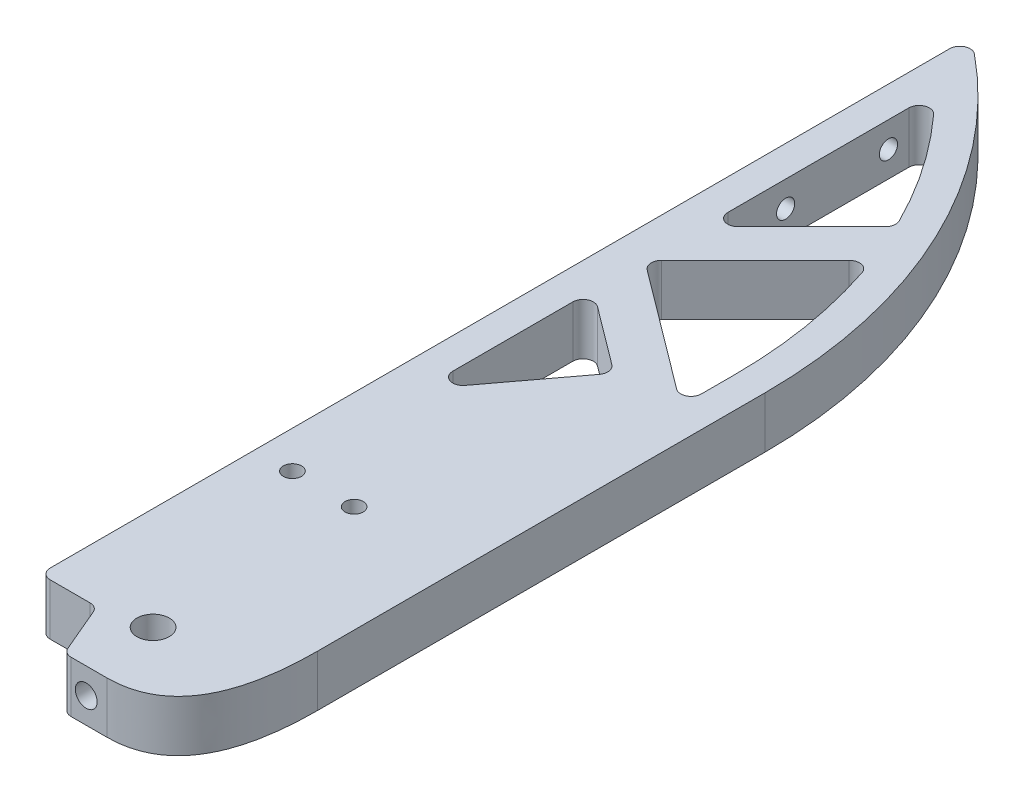
SolidWorks part; units mm, degrees
ref_plane "Front Plane" through (0, 0, 0) normal (0, 0, 1) x (1, 0, 0)
ref_plane "Top Plane" through (0, 0, 0) normal (0, 1, 0) x (1, 0, 0)
ref_plane "Right Plane" through (0, 0, 0) normal (1, 0, 0) x (0, 0, -1)
sketch "Sketch1" plane through (0, 0, 0) normal (0, 1, 0) x (1, 0, 0)
  line L1 (-25.4, -121.92) -> (25.4, -121.92)
  line L2 (-25.4, -121.92) -> (-25.4, 121.92)
  line L3 (-25.4, 121.92) -> (25.4, 121.92)
  line L4 (25.4, -121.92) -> (25.4, 121.92)
  line L5 (-25.4, -121.92) -> (25.4, 121.92) construction
  line L6 (-25.4, 121.92) -> (25.4, -121.92) construction
  point P0 (0, 0)
  dimension "D1" = 243.84
  dimension "D2" = 50.8
extrude "Boss-Extrude1" add sketch "Sketch1" along normal mid plane 12.7
sketch "Sketch2" plane through (0, 6.35, 0) normal (0, 1, 0) x (1, 0, 0)
  line L0 (0, 121.92) -> (0, -121.92) construction
  line L1 (25.4, 121.92) -> (-25.4, 121.92) construction
  line L2 (-25.4, -121.92) -> (25.4, -121.92) construction
  circle A0 centre (0, -105.41) radius 4
  dimension "D1" = 8
  dimension "D2" = 16.51
extrude "Pivot Point" cut sketch "Sketch2" against normal through all
sketch "Sketch3" plane through (0, 6.35, 0) normal (0, 1, 0) x (1, 0, 0)
  line L0 (0, -105.41) -> (0, -113.03) construction
  line L1 (0, -113.03) -> (-25.4, -113.03) construction
  line L2 (-25.4, 121.92) -> (-25.4, -121.92) construction
  line L3 (-25.4, -113.03) -> (-11.176, -113.03) construction
  line L4 (-11.176, -113.03) -> (-11.176, -121.92) construction
  line L5 (-25.4, -121.92) -> (25.4, -121.92) construction
  line L6 (-25.4, -107.95) -> (-9.8374, -107.95)
  line L7 (-9.8374, -107.95) -> (0, -105.41) construction
  line L8 (-6.7202, -113.03) -> (-2.9466, -121.92) construction
  line L10 (-25.4, -88.9) -> (-17.78, -88.9)
  line L11 (-17.78, -88.9) -> (-25.4, -25.4)
  line L12 (-25.4, -25.4) -> (-25.4, 121.92)
  line L13 (-25.4, 121.92) -> (25.4, 121.92)
  line L14 (25.4, 121.92) -> (25.4, 20.32)
  line L15 (25.4, -121.92) -> (25.4, 121.92) construction
  line L16 (25.4, -90.17) -> (25.4, -121.92)
  line L17 (25.4, -121.92) -> (5.08, -121.92)
  line L18 (-2.9466, -121.92) -> (-25.4, -121.92) construction
  line L19 (-25.4, -121.92) -> (-25.4, -25.4)
  line L21 (-11.3324, -107.95) -> (-5.4025, -121.92)
  line L22 (-5.4025, -121.92) -> (-25.4, -121.92)
  line L23 (-25.4, -25.4) -> (-25.4, -88.9)
  circle A0 centre (0, -105.41) radius 10.16 construction
  arc A1 (-9.8374, -107.95) -> (-6.7202, -113.03) centre (0, -105.41) ccw
  arc A2 (-25.4, 121.92) -> (25.4, 20.32) centre (-101.6, 20.32) cw
  spline S0 degree 2 poles (5.08, -121.92) (25.4, -121.92) (25.4, -90.17) knots 0 0 0 1 1 1
  line M22 (-25.4, 121.92) -> (-25.4, -121.92)
  line M23 (-25.4, -121.92) -> (25.4, -121.92)
  dimension "D1" = 7.62
  dimension "D4" = 20.32
  dimension "D6" = 7.62
  dimension "D7" = 63.5
  dimension "D9" = 31.75
  dimension "D10" = 20.32
  dimension "D11" = 101.6
  dimension "D12" = 2.2606
  dimension "D2" = 11.176
  dimension "D3" = 5.08
  dimension "D5" = 113
  dimension "D8" = 19.05
extrude "Main Shape" cut sketch "Sketch3" against normal through all contours A1 L6 L8 M22 M23 | S0 L16 L17 | A2 L14 L13 region at (-16.7977, 6.35, 115.3403)
sketch "Sketch12" plane through (-25.4, 0, 0) normal (-1, 0, 0) x (0, 0, 1)
  line L0 (-93.98, 0) -> (-68.58, 0)
  line L1 (-121.92, 6.35) -> (-121.92, -6.35) construction
  point P0 (-93.98, 0)
  point P2 (-68.58, 0)
  point P9 (-121.92, 0)
  dimension "D1" = 25.4
  dimension "D2" = 27.94
sketch "Sketch4" plane through (0, 6.35, 0) normal (0, 1, 0) x (1, 0, 0)
  line L0 (-17.78, 105.3247) -> (-17.78, 48.1747)
  line L1 (-17.78, 48.1747) -> (6.0241, 71.9788)
  line L2 (10.3072, 61.8935) -> (-17.78, 33.8062)
  line L3 (-17.78, 33.8062) -> (17.78, 7.1362)
  line L4 (17.78, 7.1362) -> (17.78, 20.32)
  line L5 (-17.78, 21.1062) -> (2.54, 5.8662)
  line L7 (-17.78, -21.2271) -> (-17.78, 21.1062)
  line L9 (2.54, 5.8662) -> (-17.78, -21.2271)
  line L32 (17.78, -90.17) -> (17.78, 20.32)
  line L33 (-17.78, 105.3247) -> (-17.78, -100.33)
  line L37 (-17.78, -100.33) -> (-6.2888, -100.33)
  line L38 (-6.2888, -100.33) -> (-0.3589, -114.3)
  line L39 (-0.3589, -114.3) -> (5.08, -114.3)
  line L40 (17.78, -90.17) -> (17.78, 20.32) construction
  line L41 (-17.78, 105.3247) -> (-17.78, -21.2271) construction
  line L45 (-17.78, -100.33) -> (-6.2888, -100.33) construction
  line L46 (-6.2888, -100.33) -> (-0.3589, -114.3) construction
  line L47 (-0.3589, -114.3) -> (5.08, -114.3) construction
  arc A0 (-17.78, 105.3247) -> (6.0241, 71.9788) centre (-101.6, 20.32) cw
  arc A1 (10.3072, 61.8935) -> (17.78, 20.32) centre (-101.6, 20.32) cw
  arc A4 (17.78, 20.32) -> (-17.78, 105.3247) centre (-101.6, 20.32) ccw
  arc A5 (17.78, 20.32) -> (-17.78, 105.3247) centre (-101.6, 20.32) ccw construction
  spline S0 degree 3 poles (123.1046, -2109.569) (-89.5866, 40.835) (-31.654, -118.9384) (7.3241, -114.149) (7.6414, -114.0986) (8.2727, -113.9711) (8.5882, -113.8935) (9.5157, -113.6165) (10.1083, -113.3735) (10.9496, -112.9016) (11.224, -112.725) (11.7446, -112.3429) (11.9914, -112.1376) (12.4605, -111.7012) (12.6828, -111.4702) (13.106, -110.9855) (13.3076, -110.7306) (13.8756, -109.9475) (14.2074, -109.4003) (14.8046, -108.2703) (15.0698, -107.6875) (15.5487, -106.4943) (15.7616, -105.8857) (16.3305, -104.0559) (16.6225, -102.8205) (17.0928, -100.3295) (17.2703, -99.0737) (17.5409, -96.5473) (17.6338, -95.2758) (21.9617, -2.9783) (-143.3699, 92.1841) (1998.5596, 131.0136) knots -3.730233 -3.730233 -3.730233 -3.730233 0.0625 0.0625 0.09375 0.09375 0.125 0.125 0.1875 0.1875 0.21875 0.21875 0.25 0.25 0.28125 0.28125 0.3125 0.3125 0.375 0.375 0.4375 0.4375 0.5 0.5 0.625 0.625 0.75 0.75 0.875 0.875 9.792578 9.792578 9.792578 9.792578 only from (5.08, -114.3) to (17.78, -90.17)
  spline S1 degree 3 poles (5.08, -114.3) (5.7262, -114.3) (6.3685, -114.2664) (7.3241, -114.149) (7.6414, -114.0986) (8.2727, -113.9711) (8.5882, -113.8935) (9.5157, -113.6165) (10.1083, -113.3735) (10.9496, -112.9016) (11.224, -112.725) (11.7446, -112.3429) (11.9914, -112.1376) (12.4605, -111.7012) (12.6828, -111.4702) (13.106, -110.9855) (13.3076, -110.7306) (13.8756, -109.9475) (14.2074, -109.4003) (14.8046, -108.2703) (15.0698, -107.6875) (15.5487, -106.4943) (15.7616, -105.8857) (16.3305, -104.0559) (16.6225, -102.8205) (17.0928, -100.3295) (17.2703, -99.0737) (17.5409, -96.5473) (17.6338, -95.2758) (17.7535, -92.724) (17.78, -91.4473) (17.78, -90.17) knots 0 0 0 0 0.0625 0.0625 0.09375 0.09375 0.125 0.125 0.1875 0.1875 0.21875 0.21875 0.25 0.25 0.28125 0.28125 0.3125 0.3125 0.375 0.375 0.4375 0.4375 0.5 0.5 0.625 0.625 0.75 0.75 0.875 0.875 1 1 1 1 construction
  dimension "D2" = 119.38
  dimension "D3" = 45
  dimension "D4" = 57.15
  dimension "D5" = 10.16
  dimension "D6" = 44.45
  dimension "D7" = 25.4
  dimension "D8" = 10.16
  dimension "D1" = 7.62
extrude "Optimizing Weight Cutout" cut sketch "Sketch4" against normal through all contours A1 L2 L3 L4 | L7 L5 | L1 A0 L0 region at (4.6512, 6.35, -34.4305) region at (-11.0067, 6.35, -1.9151)
hole_wizard "#8 Clearance Hole1" positions "Sketch12" profile "Sketch11" hole size "#8" standard "ANSI Inch" end condition up to next
sketch "Sketch11" plane through (-25.4, 0, -93.98) normal (0, 1, 0) x (0, 0, 1)
  line L0 (0, 0) -> (0, 27.2563)
  line L1 (0, 27.2563) -> (2.2479, 27.2563)
  line L2 (2.2479, 27.2563) -> (2.2479, 0)
  line L5 (2.2479, 0) -> (0, 0)
  line L11 (0, -6.35) -> (0, 107.95) construction
  dimension "Thru Hole Dia." = 4.4958
  dimension "Thru Hole Depth" = 27.2563
sketch "Sketch7" plane through (0, 0, 121.92) normal (0, 0, 1) x (1, 0, 0)
  point P0 (0, 0)
hole_wizard "1/4-28 Tapped Hole1" positions "Sketch7" profile "Sketch8" tap size "1/4-28" standard "ANSI Inch"
sketch "Sketch8" plane through (0, 0, 121.92) normal (1, 0, 0) x (0, -1, 0)
  line L0 (0, 0) -> (0, 15.5954)
  line L1 (0, 15.5954) -> (2.7051, 13.97)
  line L2 (2.7051, 13.97) -> (2.7051, 0)
  line L5 (2.7051, 0) -> (0, 0)
  line L10 (0, 15.5954) -> (-2.7051, 13.97) construction
  line L11 (0, -6.35) -> (0, 107.95) construction
  dimension "Tap Drill Dia." = 5.4102
  dimension "Tap Drill Depth" = 13.97
  dimension "Drill Angle" = 118
cosmetic thread "Hole Thread1" parameters "D1"=12.7, "D2"=6.35
sketch "Set Screw Ref" plane through (0, 6.35, 0) normal (0, 1, 0) x (1, 0, 0)
  line L0 (0, -105.41) -> (0, -121.92) construction
  line L1 (-5.4025, -121.92) -> (5.08, -121.92) construction
  line L2 (0, -121.92) -> (0, -107.505)
  line L3 (0, -109.41) -> (1.778, -109.41)
  circle A0 centre (0, -105.41) radius 4 construction
  dimension "D1" = 1.905
  dimension "D2" = 1.778
fillet "Fillet1" radius 2.54 13 edges at (-25.4, 0, 107.95) (-5.4025, 0, 121.92) (-25.4, 0, -121.92) (-17.78, 0, -105.3247) (-17.78, 0, -48.1747) (6.0241, 0, -71.9788) (10.3072, 0, -61.8935) (-17.78, 0, -21.1062) (17.78, 0, -7.1362) (-17.78, 0, -33.8062) (-11.3324, 0, 107.95) (2.54, 0, -5.8662) (-17.78, 0, 21.2271)
sketch "Sketch15" plane through (0, 6.35, 0) normal (0, 1, 0) x (1, 0, 0)
  line L0 (-16.2052, -54.7915) -> (-0.9652, -54.7915)
  line L3 (25.4, -90.17) -> (25.4, 20.32) construction
  point P67 (-16.2052, -54.7915)
  point P70 (-0.9652, -54.7915)
  dimension "D1" = 15.24
  dimension "D2" = 54.8
  dimension "D3" = 26.3652
hole_wizard "#8 Clearance Hole2" positions "Sketch15" profile "Sketch14" hole size "#8" standard "ANSI Inch" end condition through all
sketch "Sketch14" plane through (-16.2052, 6.35, 54.7915) normal (1, 0, 0) x (0, 0, 1)
  line L0 (0, 0) -> (0, 12.7)
  line L1 (0, 12.7) -> (2.2479, 12.7)
  line L2 (2.2479, 12.7) -> (2.2479, 0)
  line L5 (2.2479, 0) -> (0, 0)
  line L11 (0, -6.35) -> (0, 107.95) construction
  dimension "Thru Hole Dia." = 4.4958
  dimension "Thru Hole Depth" = 12.7
